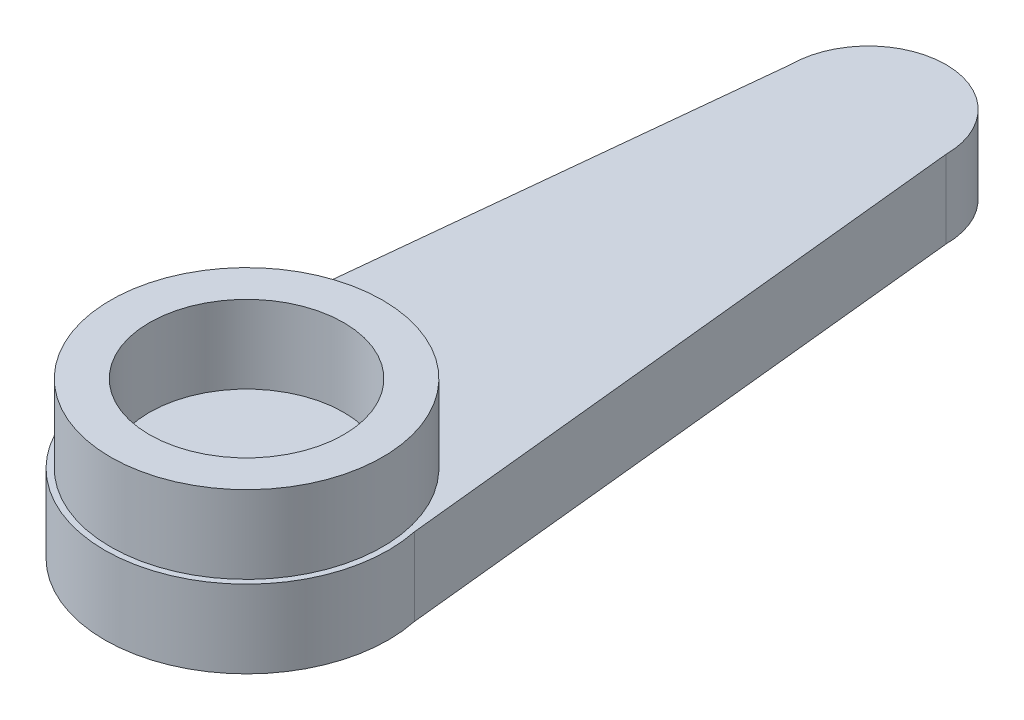
SolidWorks part; units mm, degrees
ref_plane "Front Plane" through (0, 0, 0) normal (0, 0, 1) x (1, 0, 0)
ref_plane "Top Plane" through (0, 0, 0) normal (0, 1, 0) x (1, 0, 0)
ref_plane "Right Plane" through (0, 0, 0) normal (1, 0, 0) x (0, 0, -1)
sketch "Sketch1" plane through (0, 0, 0) normal (0, 1, 0) x (1, 0, 0)
  line L2 (0, -8) -> (0, 8) construction
  line L3 (-3.5732, -7.2551) -> (-2, 8)
  line L4 (3.5732, -7.2551) -> (2, 8)
  arc A4 (-3.5732, -7.2551) -> (3.5732, -7.2551) centre (0, -8) ccw
  arc A5 (2, 8) -> (-2, 8) centre (0, 8) ccw
  point P4 (0, 0)
  dimension "D1" = 7.3
  dimension "D2" = 4
  dimension "D4" = 7.1464
  dimension "D3" = 3.5732
  dimension "D5" = 3.6307
extrude "Boss-Extrude1" add sketch "Sketch1" against normal blind 2 contours L4 A5 L3 A4
sketch "Sketch2" plane through (0, 0, 0) normal (0, 1, 0) x (1, 0, 0)
  circle A0 centre (0, -8) radius 3.5
  dimension "D1" = 7
extrude "Boss-Extrude2" add sketch "Sketch2" along normal blind 2
sketch "Sketch3" plane through (0, 2, 0) normal (0, 1, 0) x (1, 0, 0)
  circle A0 centre (0, -8) radius 2.5
  dimension "D1" = 5
extrude "Cut-Extrude1" cut sketch "Sketch3" against normal blind 2
